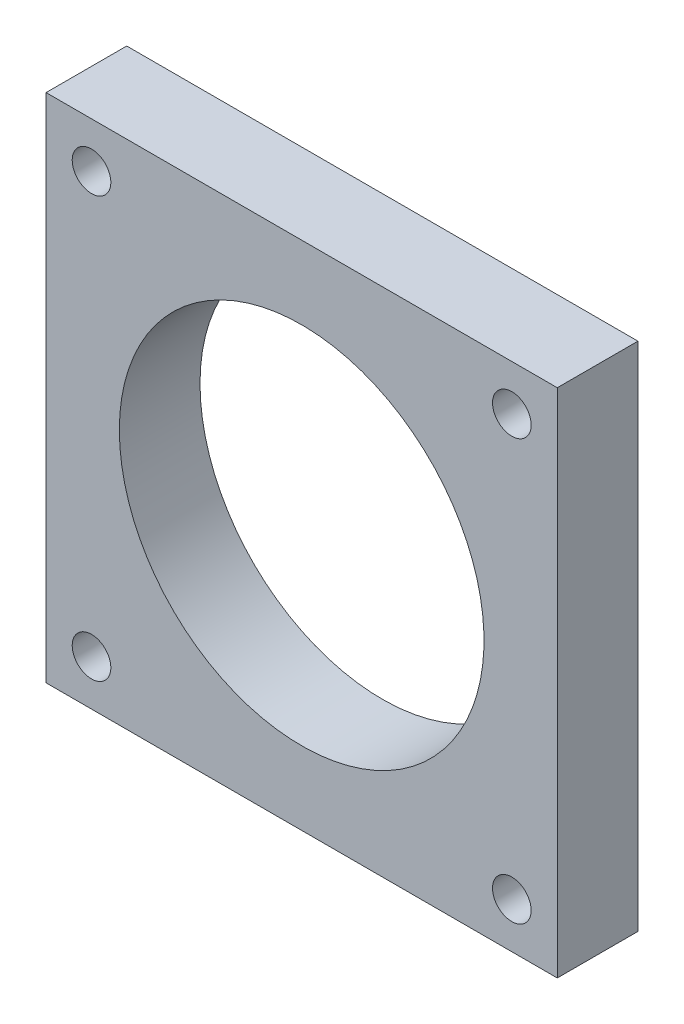
SolidWorks part; units mm, degrees
ref_plane "Front Plane" through (0, 0, 0) normal (0, 0, 1) x (1, 0, 0)
ref_plane "Top Plane" through (0, 0, 0) normal (0, 1, 0) x (1, 0, 0)
ref_plane "Right Plane" through (0, 0, 0) normal (1, 0, 0) x (0, 0, -1)
sketch "Sketch1" plane through (0, 0, 0) normal (0, 0, 1) x (1, 0, 0)
  line L1 (-22.5, -22.5) -> (22.5, -22.5)
  line L2 (-22.5, -22.5) -> (-22.5, 22.5)
  line L3 (-22.5, 22.5) -> (22.5, 22.5)
  line L4 (22.5, -22.5) -> (22.5, 22.5)
  line L5 (-22.5, -22.5) -> (22.5, 22.5) construction
  line L6 (-22.5, 22.5) -> (22.5, -22.5) construction
  circle A0 centre (0, 0) radius 16
  point P0 (0, 0)
  dimension "D3" = 32
  dimension "D1" = 45
  dimension "D2" = 45
extrude "Boss-Extrude1" add sketch "Sketch1" along normal blind 7.1
hole_wizard "M3x0.5 Tapped Hole1" positions "Sketch2" profile "Sketch3" tap size "M3x0.5" standard "ANSI Metric"
sketch "Sketch2" plane through (0, 0, 0) normal (0, 0, -1) x (-1, 0, 0)
  line L16 (-18.5, 18.5) -> (-18.5, -18.5)
  line L17 (-18.5, -18.5) -> (18.5, -18.5)
  line L18 (18.5, -18.5) -> (18.5, 18.5)
  line L19 (18.5, 18.5) -> (-18.5, 18.5)
  point P25 (-18.5, 18.5)
  point P26 (-18.5, -18.5)
  point P27 (18.5, -18.5)
  point P28 (18.5, 18.5)
sketch "Sketch3" plane through (18.5, 18.5, 0) normal (1, 0, 0) x (0, 1, 0)
  line L0 (0, 0) -> (0, 15.7511)
  line L1 (0, 15.7511) -> (1.25, 15)
  line L2 (1.25, 15) -> (1.25, 0)
  line L3 (1.25, 0) -> (0, 0)
  line L4 (0, 15.7511) -> (-1.25, 15) construction
  line L5 (0, -6.35) -> (0, 107.95) construction
  dimension "Tap Drill Dia." = 2.5
  dimension "Tap Drill Depth" = 15
  dimension "Drill Angle" = 118
cosmetic thread "Hole Thread1"
cosmetic thread "Hole Thread2"
cosmetic thread "Hole Thread3"
cosmetic thread "Hole Thread4"
hole_wizard "CBORE for M3 SHCS1" positions "Sketch4" profile "Sketch5" counterbore size "M3" standard "ANSI Metric"
sketch "Sketch4" plane through (0, 0, 0) normal (0, 0, -1) x (-1, 0, 0)
  point P0 (-18.5, 18.5)
  point P3 (18.5, 18.5)
  point P6 (18.5, -18.5)
  point P9 (-18.5, -18.5)
sketch "Sketch5" plane through (18.5, 18.5, 0) normal (1, 0, 0) x (0, 1, 0)
  line L0 (0, 0) -> (0, 8.1215)
  line L1 (0, 8.1215) -> (1.7, 7.1)
  line L2 (1.7, 7.1) -> (1.7, 3)
  line L3 (1.7, 3) -> (3.25, 3)
  line L4 (3.25, 3) -> (3.25, 0)
  line L5 (3.25, 0) -> (0, 0)
  line L6 (0, 8.1215) -> (-1.7, 7.1) construction
  line L7 (0, -6.35) -> (0, 107.95) construction
  dimension "Hole Dia." = 3.4
  dimension "Hole Depth" = 7.1
  dimension "C'Bore Dia." = 6.5
  dimension "C'Bore Depth" = 3
  dimension "Drill Angle" = 118
other "3D Printing Tolerance" flip direction yes face at (16, 0, 7.1) offset 0.05 parameters "D1"=0.05
